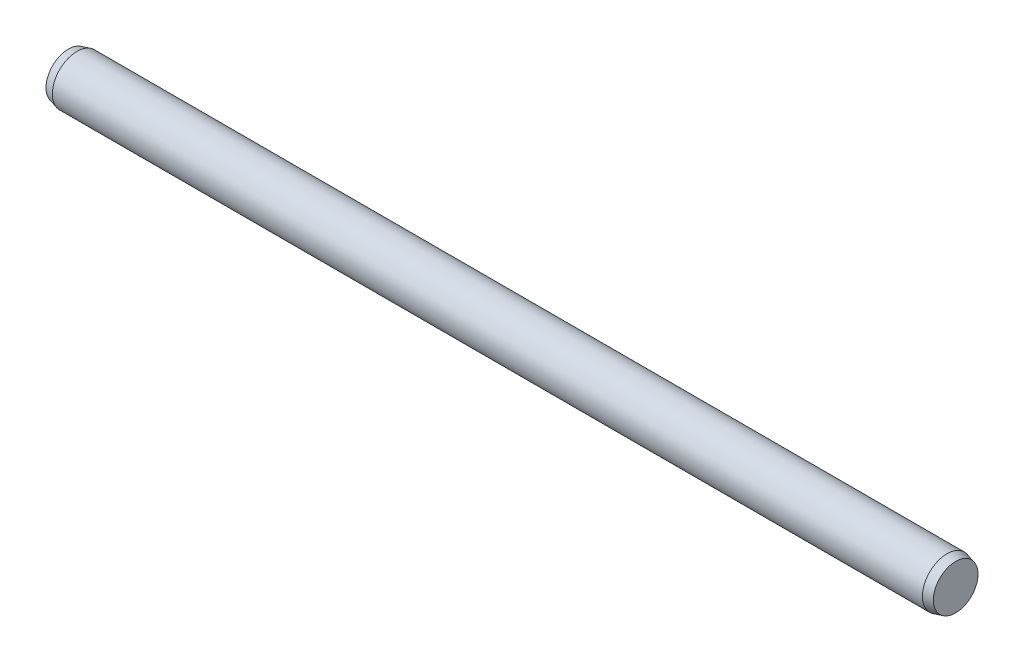
SolidWorks part; units mm, degrees
ref_plane "Front Plane" through (0, 0, 0) normal (0, 0, 1) x (1, 0, 0)
ref_plane "Top Plane" through (0, 0, 0) normal (0, 1, 0) x (1, 0, 0)
ref_plane "Right Plane" through (0, 0, 0) normal (1, 0, 0) x (0, 0, -1)
sketch "Sketch1" plane through (0, 0, 0) normal (0, 0, 1) x (1, 0, 0)
  line L0 (-17.65, 0) -> (17.65, 0) construction
  line L1 (17.65, 1) -> (17.65, -1) construction
  line L2 (-17.65, 1) -> (-17.65, -1) construction
  line L3 (18, 1) -> (18, -1) construction
  line L4 (-18, 1) -> (-18, -1) construction
  line L5 (-17.65, 0) -> (-18, 0) construction
  line L6 (17.65, 0) -> (18, 0) construction
  dimension "D1" = 0.35
  dimension "Dia" = 2
  dimension "Length" = 36
  dimension "C" = 0.35
sketch "Sketch2" plane through (0, 0, 0) normal (1, 0, 0) x (0, 0, -1)
  circle A0 centre (0, 0) radius 1
extrude "Extrude1" add sketch "Sketch2" against normal up to vertex (17.65 mm away) and the other way up to vertex (17.65 mm away) up to point (-17.65, 1, 0) other way up to point (17.65, 1, 0)
sketch "Sketch3" plane through (17.65, 0, 0) normal (1, 0, 0) x (0, 0, -1)
  circle A1 centre (0, 0) radius 1
  circle A2 centre (0, 0) radius 1
  dimension "D1" = 0
extrude "Extrude2" add sketch "Sketch3" along normal up to vertex (0.35 mm away) draft 15 up to point (18, 0, 0)
sketch "Sketch4" plane through (-17.65, 0, 0) normal (-1, 0, 0) x (0, 0, 1)
  circle A1 centre (0, 0) radius 1
  circle A2 centre (0, 0) radius 1
  dimension "D1" = 0
extrude "Extrude3" add sketch "Sketch4" along normal up to vertex (0.35 mm away) draft 15 up to point (-18, 0, 0)
equation "\"D1@Sketch1\" = \"C@Sketch1\""
